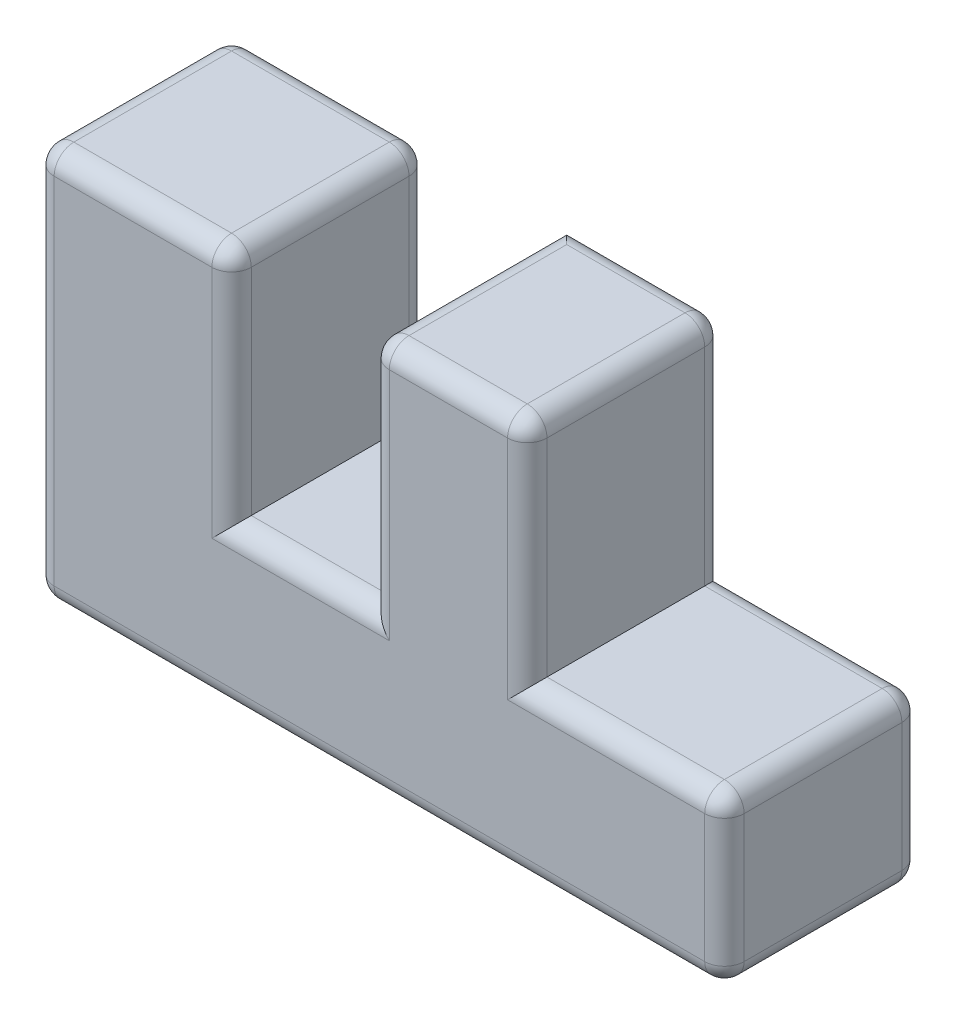
SolidWorks part; units mm, degrees
ref_plane "Front Plane" through (0, 0, 0) normal (0, 0, 1) x (1, 0, 0)
ref_plane "Top Plane" through (0, 0, 0) normal (0, 1, 0) x (1, 0, 0)
ref_plane "Right Plane" through (0, 0, 0) normal (1, 0, 0) x (0, 0, -1)
sketch "Sketch1" plane through (0, 0, 0) normal (0, 0, 1) x (1, 0, 0)
  line L0 (0, 0) -> (0, 50.8)
  line L1 (0, 50.8) -> (25.4, 50.8)
  line L2 (25.4, 50.8) -> (25.4, 20.5619)
  line L3 (25.4, 20.5619) -> (43.18, 20.5619)
  line L4 (43.18, 20.5619) -> (43.18, 50.8)
  line L5 (43.18, 50.8) -> (63.5, 50.8)
  line L6 (63.5, 50.8) -> (63.5, 21.59)
  line L7 (63.5, 21.59) -> (88.9, 21.59)
  line L8 (88.9, 21.59) -> (88.9, 0)
  line L9 (88.9, 0) -> (0, 0)
  dimension "D1" = 25.4
  dimension "D2" = 63.5
  dimension "D3" = 20.32
  dimension "D4" = 88.9
  dimension "D5" = 50.8
  dimension "D6" = 21.59
  dimension "D7" = 20.5619
extrude "Boss-Extrude2" add sketch "Sketch1" along normal blind 25.4
fillet "Fillet4" radius 2.54 1 edges at (12.7, 50.8, 25.4)
fillet "Fillet5" radius 2.54 20 edges at (0, 24.13, 25.4) (0, 50.0561, 24.6561) (25.4, 34.411, 25.4) (25.4, 50.0561, 24.6561) (63.5, 50.8, 12.7) (53.34, 50.8, 25.4) (43.18, 50.8, 12.7) (53.34, 50.8, 0) (0, 50.8, 11.43) (88.9, 21.59, 12.7) (76.2, 21.59, 0) (76.2, 21.59, 25.4) (63.5, 36.195, 0) (63.5, 36.195, 25.4) (43.18, 35.681, 25.4) (34.29, 20.5619, 0) (34.29, 20.5619, 25.4) (25.4, 35.681, 0) (25.4, 50.8, 11.43) (12.7, 50.8, 0)
fillet "Fillet6" radius 2.54 11 edges at (88.1561, 20.8461, 24.6561) (45.72, 0, 25.4) (0.7439, 0, 24.6561) (88.1561, 20.8461, 0.7439) (0.7439, 50.0561, 0.7439) (88.9, 9.525, 25.4) (88.9, 0, 12.7) (0, 0, 11.43) (88.9, 9.525, 0) (44.45, 0, 0) (0, 24.13, 0)
